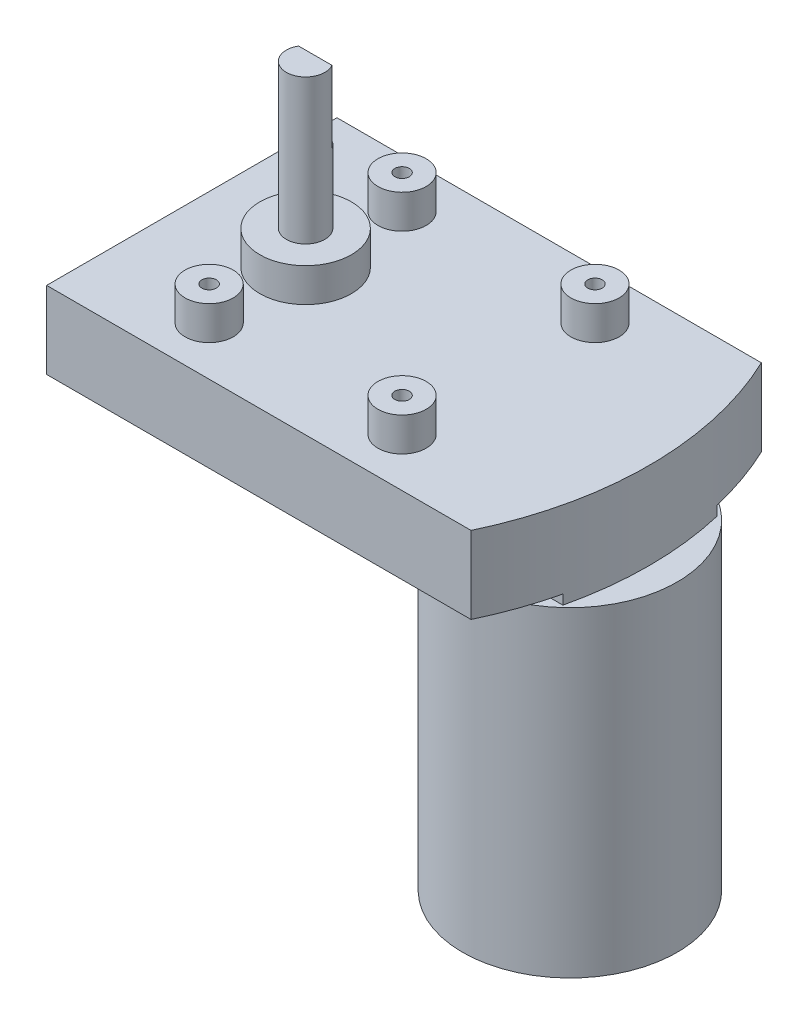
SolidWorks part; units mm, degrees
ref_plane "前视基准面" through (0, 0, 0) normal (0, 0, 1) x (1, 0, 0)
ref_plane "上视基准面" through (0, 0, 0) normal (0, 1, 0) x (1, 0, 0)
ref_plane "右视基准面" through (0, 0, 0) normal (1, 0, 0) x (0, 0, -1)
sketch "草图1" plane through (0, 0, 0) normal (0, 1, 0) x (1, 0, 0)
  line L0 (0, 0) -> (26.1254, 0) construction
  line L1 (-44, -30.1) -> (44, -30.1)
  line L2 (-44, -30.1) -> (-44, 30.1)
  line L3 (-44, 30.1) -> (44, 30.1)
  line L4 (44, -30.1) -> (44, 30.1)
  line L5 (-44, -30.1) -> (44, 30.1) construction
  line L6 (-44, 30.1) -> (44, -30.1) construction
  line L8 (19.6, -20) -> (-20.4, -20) construction
  line L9 (19.6, -20) -> (19.6, 20) construction
  line L10 (19.6, 20) -> (-20.4, 20) construction
  line L11 (-20.4, -20) -> (-20.4, 20) construction
  circle A0 centre (-20.4, 20) radius 5
  circle A1 centre (19.6, 20) radius 5
  circle A2 centre (19.6, -20) radius 5
  circle A3 centre (-20.4, -20) radius 5
  circle A4 centre (-20.4, 0) radius 9.5
  point P0 (0, 0)
  point P8 (0, 0)
  dimension "D4" = 10
  dimension "D5" = 19
  dimension "D1" = 60.2
  dimension "D2" = 88
  dimension "D3" = 40
  dimension "D6" = 23.6
extrude "凸台-拉伸1" add sketch "草图1" along normal blind 16 contours L2 L3 L4 L1
extrude "凸台-拉伸3" add sketch "草图1<4>" along normal blind 23 contours A3 | A4 | A0 | A1 | A2
sketch "草图1<4>" plane through (0, 0, 0) normal (0, 1, 0) x (1, 0, 0) same geometry as "草图1"
sketch "草图2" plane through (0, 23, 0) normal (0, 1, 0) x (1, 0, 0)
  circle A0 centre (-20.4, 0) radius 4
  dimension "D1" = 8
extrude "凸台-拉伸4" add sketch "草图2" along normal blind 30
sketch "草图3" plane through (0, 53, 0) normal (0, 1, 0) x (1, 0, 0)
  line L0 (-20.4, -4) -> (-20.4, 2) construction
  line L1 (-23.8641, 2) -> (-16.9359, 2)
  circle A0 centre (-20.4, 0) radius 4 construction
  arc A1 (-16.9359, 2) -> (-23.8641, 2) centre (-20.4, 0) ccw
  dimension "D1" = 6
extrude "切除-拉伸3" cut sketch "草图3" against normal blind 15
sketch "草图4" plane through (0, 23, 0) normal (0, 1, 0) x (1, 0, 0)
  circle A0 centre (-20.4, 20) radius 1.5
  circle A1 centre (19.6, 20) radius 1.5
  circle A2 centre (19.6, -20) radius 1.5
  circle A3 centre (-20.4, -20) radius 1.5
  dimension "D1" = 3
extrude "切除-拉伸4" cut sketch "草图4" against normal blind 10
sketch "草图5" plane through (0, 0, 0) normal (0, 1, 0) x (1, 0, 0)
  line L1 (44, -30.1) -> (50.802, -30.1) construction
  line L2 (50.802, -30.1) -> (50.802, 12.7482) construction
  line L7 (-44, -30.1) -> (44, -30.1)
  line L8 (44, -30.1) -> (44, 30.1)
  line L9 (44, 30.1) -> (-44, 30.1)
  line L10 (-44, 30.1) -> (-44, -30.1)
  line L13 (44, -30.1) -> (44, 30.1)
  arc A0 (44, -30.1) -> (44, 30.1) centre (-19.198, 0) ccw
  dimension "D1" = 0
  dimension "D2" = 70
extrude "凸台-拉伸6" add sketch "草图5" along normal up to surface (16 mm away) up to face at (19.6, 16, 25)
sketch "草图6" plane through (0, 0, 0) normal (0, -1, 0) x (1, 0, 0)
  line L1 (18, -16) -> (48.9489, -16)
  line L2 (18, -16) -> (18, 16)
  line L3 (18, 16) -> (48.9489, 16)
  line L5 (18, -16) -> (44, 16) construction
  line L6 (18, 16) -> (44, -16) construction
  arc A0 (44, -30.1) -> (44, 30.1) centre (-19.198, 0) ccw construction
  arc A1 (48.9489, -16) -> (48.9489, 16) centre (-19.198, 0) ccw
  point P0 (31, 0)
  dimension "D1" = 32
  dimension "D2" = 26
extrude "凸台-拉伸7" add sketch "草图6" along normal blind 2
sketch "草图7" plane through (0, -2, 0) normal (0, -1, 0) x (1, 0, 0)
  line L0 (18, 0) -> (50.802, 0) construction
  line L1 (18, 16) -> (18, -16) construction
  arc A0 (48.9489, -16) -> (48.9489, 16) centre (-19.198, 0) ccw construction
  circle A1 centre (34.401, 0) radius 22.25
  dimension "D1" = 44.5
extrude "凸台-拉伸8" add sketch "草图7" along normal blind 66.5
sketch "草图8" plane through (0, 23, 0) normal (0, 1, 0) x (1, 0, 0)
  line L0 (-23.8641, 2) -> (-16.9359, 2) construction
  circle A0 centre (-20.4, 0) radius 4
